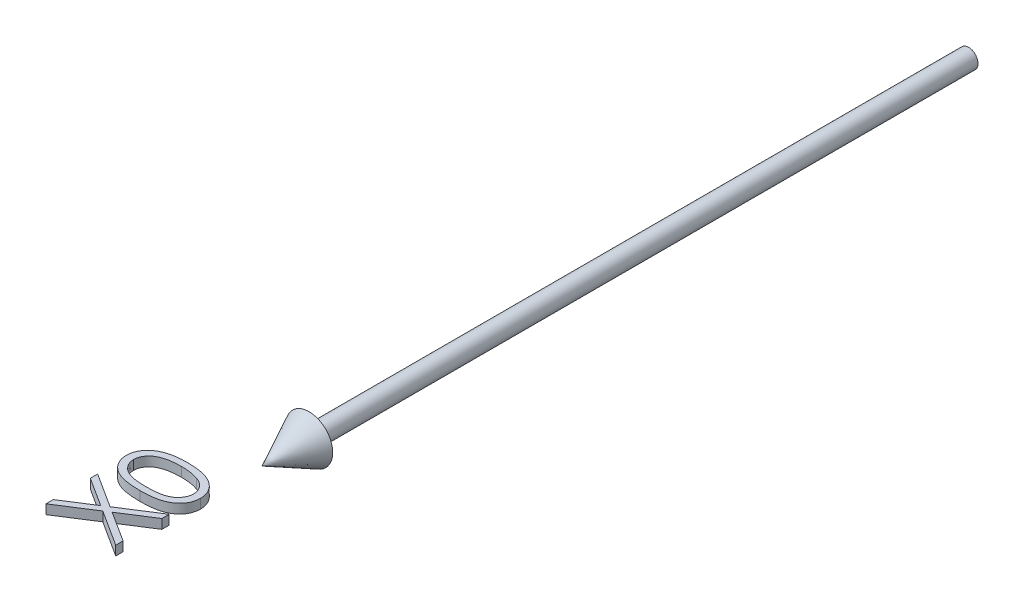
SolidWorks part; units mm, degrees
ref_plane "Front Plane" through (0, 0, 0) normal (0, 0, 1) x (1, 0, 0)
ref_plane "Top Plane" through (0, 0, 0) normal (0, 1, 0) x (1, 0, 0)
ref_plane "Right Plane" through (0, 0, 0) normal (1, 0, 0) x (0, 0, -1)
sketch "Sketch2" plane through (0, 0, 0) normal (0, 1, 0) x (1, 0, 0)
  line L0 (0, 41.95) -> (0, -114.4521) construction
  line L1 (-36.8894, 0) -> (41.4965, 0) construction
  line L2 (0, -150) -> (5, -140)
  line L3 (5, -140) -> (2, -140)
  line L4 (2, -140) -> (2, 0)
  line L5 (2, 0) -> (0, 0)
  line L6 (0, 0) -> (0, -150)
  dimension "D1" = 150
  dimension "D2" = 2
  dimension "D3" = 10
  dimension "D4" = 5
revolve "Revolve1" add sketch "Sketch2" angle 360 about L0
sketch "Sketch3" plane through (0, 0, 0) normal (0, 1, 0) x (1, 0, 0)
  line L0 (0, -157.5) -> (0, -309.0844) construction
  line L1 (-18.6107, 0) -> (18.3141, 0) construction
  text T0 "X0" font "Century Gothic" height 15
  point P3 (0, -215.0968)
  point P4 (0, -309.0844)
  point P8 (2.5, -161.6979)
  dimension "D1" = 157.5
extrude "Boss-Extrude1" add sketch "Sketch3" against normal blind 1 and the other way blind 1 separate body
equation "\"D1@Sketch2\"=\"frame_arrow_length\""
equation "\"D2@Sketch2\"=\"frame_arrow_odA\"/2"
equation "\"D4@Sketch2\"=\"frame_arrow_head_od\""
equation "\"D3@Sketch2\"=\"frame_arrow_head_length\""
equation "\"frame_arrow_length\"=150"
equation "\"frame_arrow_head_length\"=10"
equation "\"frame_arrow_head_od\"=5"
equation "\"frame_arrow_odA\"=4"
equation "\"D1@Sketch3\"=\"frame_arrow_length\"*1.05"
